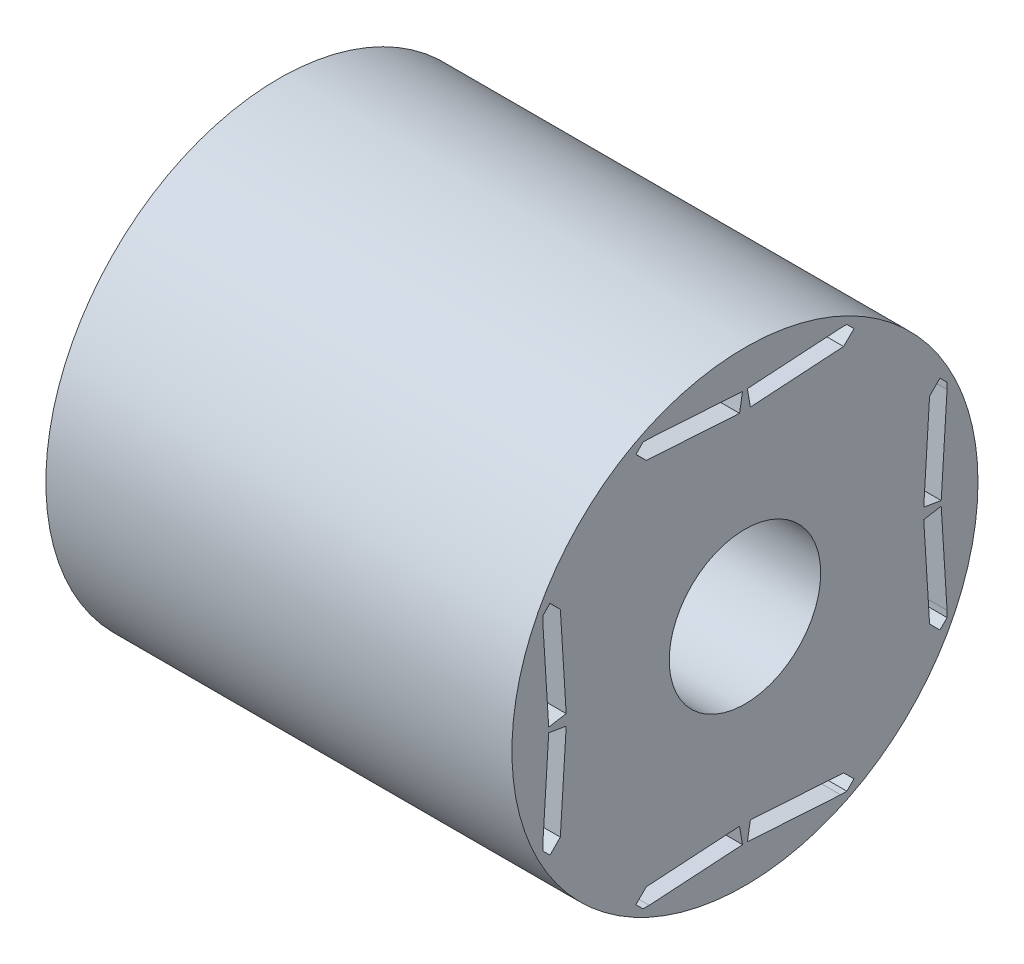
SolidWorks part; units mm, degrees
ref_plane "Front Plane" through (0, 0, 0) normal (0, 0, 1) x (1, 0, 0)
ref_plane "Top Plane" through (0, 0, 0) normal (0, 1, 0) x (1, 0, 0)
ref_plane "Right Plane" through (0, 0, 0) normal (1, 0, 0) x (0, 0, -1)
sketch "Sketch1" plane through (0, 0, 0) normal (1, 0, 0) x (0, 0, -1)
  circle A3 centre (0, 0) radius 100
  dimension "D1" = 200
extrude "Boss-Extrude1" add sketch "Sketch1" along normal blind 10 contours A3
sketch "Sketch2" plane through (10, 0, 0) normal (1, 0, 0) x (0, 0, -1)
  line L4 (0, 0) -> (0, 109.3967) construction
  line L5 (-177.6356, 0) -> (198.2815, 0) construction
  line L14 (1.0478, 84.2125) -> (2.3219, 76.7125)
  line L15 (1.0478, 84.2125) -> (41.0478, 86.7272)
  line L16 (2.3219, 76.7125) -> (42.3219, 79.2272)
  line L18 (41.0478, 86.7272) -> (43.7204, 86.7272)
  line L19 (43.7204, 86.7272) -> (46.7966, 83.651)
  line L20 (46.7966, 83.651) -> (42.3219, 79.2272)
  line L21 (-1.0478, 84.2125) -> (-2.3219, 76.7125)
  line L22 (-2.3219, 76.7125) -> (-42.3219, 79.2272)
  line L23 (-46.7966, 83.651) -> (-42.3219, 79.2272)
  line L24 (-43.7204, 86.7272) -> (-46.7966, 83.651)
  line L25 (-41.0478, 86.7272) -> (-43.7204, 86.7272)
  line L26 (-1.0478, 84.2125) -> (-41.0478, 86.7272)
  line L27 (84.2125, 1.0478) -> (76.7125, 2.3219)
  line L28 (76.7125, 2.3219) -> (79.2272, 42.3219)
  line L29 (83.651, 46.7966) -> (79.2272, 42.3219)
  line L30 (86.7272, 43.7204) -> (83.651, 46.7966)
  line L31 (86.7272, 41.0478) -> (86.7272, 43.7204)
  line L32 (84.2125, 1.0478) -> (86.7272, 41.0478)
  line L33 (84.2125, -1.0478) -> (86.7272, -41.0478)
  line L34 (86.7272, -41.0478) -> (86.7272, -43.7204)
  line L35 (86.7272, -43.7204) -> (83.651, -46.7966)
  line L36 (83.651, -46.7966) -> (79.2272, -42.3219)
  line L37 (76.7125, -2.3219) -> (79.2272, -42.3219)
  line L38 (84.2125, -1.0478) -> (76.7125, -2.3219)
  line L39 (1.0478, -84.2125) -> (2.3219, -76.7125)
  line L40 (2.3219, -76.7125) -> (42.3219, -79.2272)
  line L41 (46.7966, -83.651) -> (42.3219, -79.2272)
  line L42 (43.7204, -86.7272) -> (46.7966, -83.651)
  line L43 (41.0478, -86.7272) -> (43.7204, -86.7272)
  line L44 (1.0478, -84.2125) -> (41.0478, -86.7272)
  line L45 (-1.0478, -84.2125) -> (-41.0478, -86.7272)
  line L46 (-41.0478, -86.7272) -> (-43.7204, -86.7272)
  line L47 (-43.7204, -86.7272) -> (-46.7966, -83.651)
  line L48 (-46.7966, -83.651) -> (-42.3219, -79.2272)
  line L49 (-2.3219, -76.7125) -> (-42.3219, -79.2272)
  line L50 (-1.0478, -84.2125) -> (-2.3219, -76.7125)
  line L51 (-84.2125, -1.0478) -> (-76.7125, -2.3219)
  line L52 (-76.7125, -2.3219) -> (-79.2272, -42.3219)
  line L53 (-83.651, -46.7966) -> (-79.2272, -42.3219)
  line L54 (-86.7272, -43.7204) -> (-83.651, -46.7966)
  line L55 (-86.7272, -41.0478) -> (-86.7272, -43.7204)
  line L56 (-84.2125, -1.0478) -> (-86.7272, -41.0478)
  line L57 (-84.2125, 1.0478) -> (-86.7272, 41.0478)
  line L58 (-86.7272, 41.0478) -> (-86.7272, 43.7204)
  line L59 (-86.7272, 43.7204) -> (-83.651, 46.7966)
  line L60 (-83.651, 46.7966) -> (-79.2272, 42.3219)
  line L61 (-76.7125, 2.3219) -> (-79.2272, 42.3219)
  line L62 (-84.2125, 1.0478) -> (-76.7125, 2.3219)
  circle A0 centre (0, 0) radius 32.5
  point P56 (0, 0)
  dimension "D3" = 65
  dimension "D1" = 7.5
  dimension "D2" = 40
extrude "Cut-Extrude1" cut sketch "Sketch2" against normal blind 250
pattern_linear "LPattern5" count 20 spacing 10 along (-1, 0, 0) of "Cut-Extrude1", "Boss-Extrude1"
